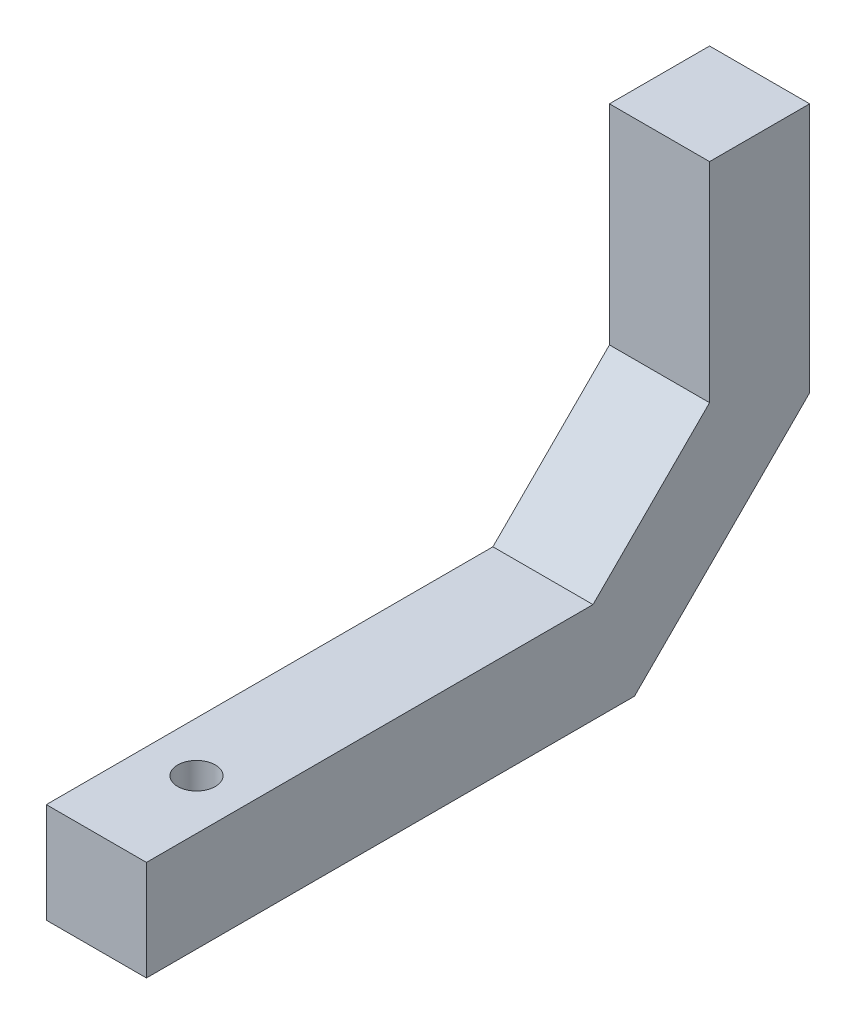
SolidWorks part; units mm, degrees
ref_plane "Front Plane" through (0, 0, 0) normal (0, 0, 1) x (1, 0, 0)
ref_plane "Top Plane" through (0, 0, 0) normal (0, 1, 0) x (1, 0, 0)
ref_plane "Right Plane" through (0, 0, 0) normal (1, 0, 0) x (0, 0, -1)
ref_axis "Z" through (0, 0, 55.65) along (0, 0, -1)
sketch "Sketch1" plane through (0, 0, 0) normal (1, 0, 0) x (0, 0, -1)
  line L0 (-8, 4) -> (0, 4)
  line L1 (0, 4) -> (0, -16)
  line L2 (0, -16) -> (-14, -30)
  line L3 (-14, -30) -> (-45, -30)
  line L4 (-45, -30) -> (-45, -22) construction
  line L5 (-45, -22) -> (-17.3137, -22)
  line L6 (-17.3137, -22) -> (-8, -12.6863)
  line L7 (-8, -12.6863) -> (-8, 4)
  line L8 (-13.4134, -18.0997) -> (-7.7566, -23.7566) construction
  line L10 (-45, -22) -> (-53, -22)
  line L11 (-45, -22) -> (-45, -30) construction
  line L12 (-45, -30) -> (-53, -30)
  line L13 (-53, -22) -> (-53, -30)
  dimension "D1" = 8
  dimension "D2" = 45
  dimension "D3" = 30
  dimension "D4" = 4
  dimension "D5" = 135
  dimension "D6" = 14
  dimension "D7" = 8
extrude "Boss-Extrude1" add sketch "Sketch1" along normal blind 4 and the other way blind 4
sketch "Sketch3" plane through (0, -22, 0) normal (0, 1, 0) x (1, 0, 0)
  line L0 (-55, 0) -> (55, 0) construction
  line L1 (0, -55) -> (0, 55) construction
  circle A0 centre (0, -45) radius 1.5
  dimension "D2" = 3
  dimension "D1" = 45
extrude "Cut-Extrude1" cut sketch "Sketch3" against normal through all
ref_axis "Axis1" through (0, -22, 45) along (0, 1, 0)
equation "\"rbracket-width\"= 8"
equation "\"D1@Boss-Extrude1\"=\"rbracket-width\"/2"
equation "\"D2@Boss-Extrude1\"=\"rbracket-width\"/2"
equation "\"EyeCaptureRadius\"= ( \"EyeDiameter\" + \"EyeClearance\" ) / 2"
equation "\"rbracket_planetocenterline_dist\"= \"BasePlaneDistance\""
equation "\"D2@Sketch1\"=\"rbracket_planetocenterline_dist\""
equation "\"EyeDiameter\" = 28"
equation "\"BasePlaneDistance\" = 45"
equation "\"EyeClearance\" = 2"
equation "\"D1@Sketch1\"=\"rbracket-width\""
equation "\"D3@Sketch1\"=(\"EyeDiameter\"+\"EyeClearance\"+\"EyeClearance\")/2 + \"L2Thickness\" + \"rbracket-width\""
equation "\"D4@Sketch1\"=\"rbracket-width\"/2"
equation "\"D6@Sketch1\"=\"EyeDiameter\"/2"
equation "\"D7@Sketch1\"=\"rbracket-width\""
equation "\"D1@Sketch3\"=\"BasePlaneDistance\""
equation "\"L2Thickness\" = 6"
